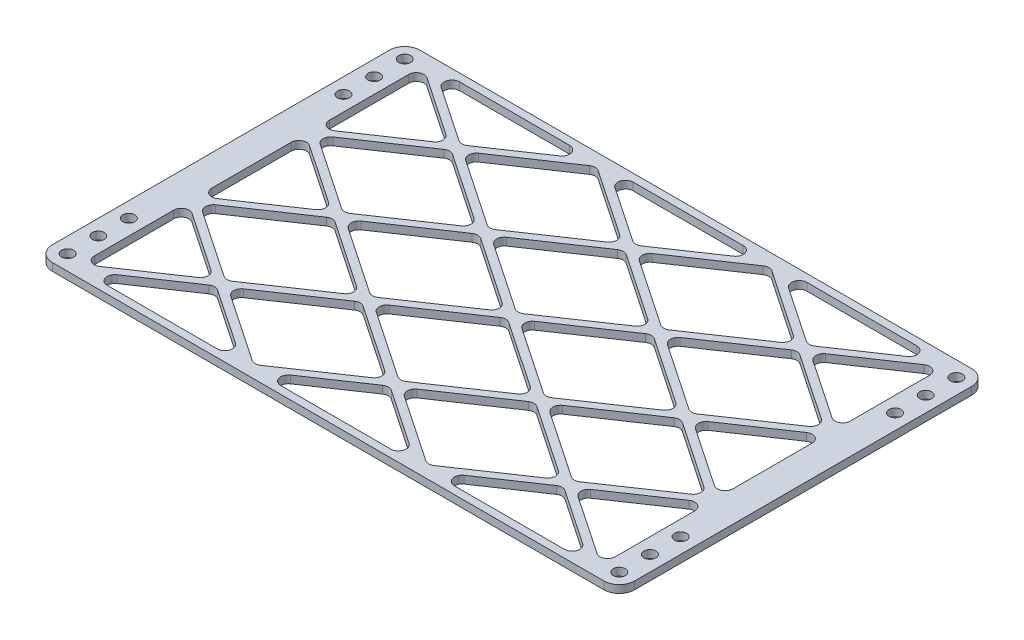
SolidWorks part; units mm, degrees
ref_plane "Front Plane" through (0, 0, 0) normal (0, 0, 1) x (1, 0, 0)
ref_plane "Top Plane" through (0, 0, 0) normal (0, 1, 0) x (1, 0, 0)
ref_plane "Right Plane" through (0, 0, 0) normal (1, 0, 0) x (0, 0, -1)
sketch "Sketch1" plane through (0, 0, 0) normal (0, 1, 0) x (1, 0, 0)
  line L0 (12.7, 152.4) -> (12.7, 0)
  line L1 (0, 0) -> (241.3, 0)
  line L2 (0, 0) -> (0, 152.4)
  line L3 (0, 152.4) -> (241.3, 152.4)
  line L4 (241.3, 0) -> (241.3, 152.4)
  line L5 (120.65, 152.4) -> (120.65, 0) construction
  line L6 (228.6, 152.4) -> (228.6, 0)
  line L7 (228.6, 3.175) -> (12.7, 149.225) construction
  line L8 (12.7, 149.225) -> (228.6, 149.225)
  line L9 (12.7, 3.175) -> (228.6, 3.175)
  line L10 (12.7, 100.5417) -> (84.6667, 100.5417)
  line L11 (84.6667, 100.5417) -> (84.6667, 149.225)
  line L12 (17.88, 147.6375) -> (15.5333, 149.225)
  line L13 (233.78, 1.5875) -> (17.88, 147.6375)
  line L14 (12.7, 100.5417) -> (84.6667, 149.225) construction
  line L15 (13.5895, 99.2268) -> (85.5562, 147.9101)
  line L16 (223.42, 4.7625) -> (7.52, 150.8125)
  line L17 (11.8105, 101.8566) -> (83.7772, 150.5399)
  line L18 (17.88, 147.6375) -> (228.6, 147.6375) construction
  line L19 (7.52, 150.8125) -> (228.6, 150.8125) construction
  line L20 (12.7, 4.7625) -> (223.42, 4.7625) construction
  line L21 (12.7, 1.5875) -> (233.78, 1.5875) construction
  circle A0 centre (6.35, 146.05) radius 2.4892
  circle A1 centre (6.35, 6.35) radius 2.4892
  dimension "D1" = 4.9784
  dimension "D2" = 139.7
  dimension "D3" = 6.35
  dimension "D4" = 6.35
  dimension "D5" = 6.35
  dimension "D6" = 241.3
  dimension "D7" = 6.35
  dimension "D8" = 3.175
  dimension "D9" = 3.175
  dimension "D10" = 71.9667
  dimension "D13" = 1.5875
  dimension "D11" = 1.5875
  dimension "D12" = 1.5875
  dimension "D14" = 1.5875
extrude "Boss-Extrude5" add sketch "Sketch1" along normal blind 3.175 contours L6 L13 L11 L10 L0 L9 | L3 L2 L1 L0 A1 A0 | L3 L6 L1 L4 | L9 L0 L1 L6 | L13 L6 L8 L11 | L13 L17 L8 L12 | L0 L8 L6 L3 | L15 L13 L11 | L17 L13 L15 L11 L8 | L17 L0 L10 L15 L16 | L17 L16 L15 L13 | L16 L17 L13 L12 L8 L0 | L16 L10 L11 L13 L15 | L0 L17 L16 | L10 L16 L15 region at (120.65, 0, -150.8125) region at (6.35, 0, -76.2) region at (30.335, 0, -137.2954) region at (234.95, 0, -76.2) region at (23.75, 0, -124.8833) region at (48.6833, 0, -141.75) region at (168.8686, 0, -97.3616) region at (30.335, 0, -112.4713) region at (48.6833, 0, -124.8833) region at (67.0316, 0, -137.2954) region at (120.65, 0, -1.5875) region at (91.9374, 0, -43.9196) region at (48.6833, 0, -108.0167) region at (67.0316, 0, -112.4713) region at (73.6166, 0, -124.8833)
extrude "Cut-Extrude7" cut sketch "Sketch1<6>" along normal blind 32.131 contours L10 L16 L15 | L0 L17 L16 | L13 L17 L8 L12 | L15 L13 L11 region at (23.75, 0, -124.8833) region at (48.6833, 0, -141.75) region at (48.6833, 0, -108.0167) region at (73.6166, 0, -124.8833)
sketch "Sketch1<6>" plane through (0, 0, 0) normal (0, 1, 0) x (1, 0, 0) same geometry as "Sketch1"
pattern_linear "LPattern3" count 3 spacing 71.9667 along (1, 0, 0) count 3 spacing 48.6833 along (0, 0, 1) of "Cut-Extrude7"
fillet "Fillet2" radius 3.175 84 edges at (156.6333, 1.5875, -49.9417) (123.4833, 1.5875, -27.5167) (156.6333, 1.5875, -5.0916) (189.7834, 1.5875, -27.5167) (84.6667, 1.5875, -49.9417) (51.5166, 1.5875, -27.5167) (84.6667, 1.5875, -5.0916) (117.8167, 1.5875, -27.5167) (45.8501, 1.5875, -27.5167) (12.7, 1.5875, -49.9417) (12.7, 1.5875, -5.0916) (156.6333, 1.5875, -147.3084) (123.4833, 1.5875, -124.8833) (156.6333, 1.5875, -102.4583) (189.7834, 1.5875, -124.8833) (45.8501, 1.5875, -76.2) (12.7, 1.5875, -98.6251) (12.7, 1.5875, -53.7749) (84.6667, 1.5875, -98.6251) (51.5166, 1.5875, -76.2) (84.6667, 1.5875, -53.7749) (117.8167, 1.5875, -76.2) (156.6333, 1.5875, -98.6251) (123.4833, 1.5875, -76.2) (156.6333, 1.5875, -53.7749) (189.7834, 1.5875, -76.2) (84.6667, 1.5875, -147.3084) (51.5166, 1.5875, -124.8833) (84.6667, 1.5875, -102.4583) (117.8167, 1.5875, -124.8833) (192.6167, 1.5875, -25.6001) (159.4666, 1.5875, -3.175) (225.7667, 1.5875, -3.175) (120.65, 1.5875, -25.6001) (87.4999, 1.5875, -3.175) (153.8001, 1.5875, -3.175) (48.6833, 1.5875, -25.6001) (15.5333, 1.5875, -3.175) (81.8334, 1.5875, -3.175) (159.4666, 1.5875, -100.5417) (192.6167, 1.5875, -78.1166) (225.7667, 1.5875, -100.5417) (192.6167, 1.5875, -122.9667) (15.5333, 1.5875, -51.8583) (48.6833, 1.5875, -29.4333) (81.8334, 1.5875, -51.8583) (48.6833, 1.5875, -74.2834) (87.4999, 1.5875, -51.8583) (120.65, 1.5875, -29.4333) (153.8001, 1.5875, -51.8583) (120.65, 1.5875, -74.2834) (159.4666, 1.5875, -51.8583) (192.6167, 1.5875, -29.4333) (225.7667, 1.5875, -51.8583) (192.6167, 1.5875, -74.2834) (87.4999, 1.5875, -100.5417) (120.65, 1.5875, -78.1166) (153.8001, 1.5875, -100.5417) (120.65, 1.5875, -122.9667) (45.8501, 1.5875, -124.8833) (12.7, 1.5875, -147.3084) (12.7, 1.5875, -102.4583) (48.6833, 1.5875, -126.7999) (15.5333, 1.5875, -149.225) (120.65, 1.5875, -126.7999) (153.8001, 1.5875, -149.225) (87.4999, 1.5875, -149.225) (48.6833, 1.5875, -78.1166) (81.8334, 1.5875, -100.5417) (48.6833, 1.5875, -122.9667) (15.5333, 1.5875, -100.5417) (192.6167, 1.5875, -126.7999) (225.7667, 1.5875, -149.225) (159.4666, 1.5875, -149.225) (195.4499, 1.5875, -76.2) (228.6, 1.5875, -53.7749) (228.6, 1.5875, -98.6251) (195.4499, 1.5875, -124.8833) (228.6, 1.5875, -102.4583) (228.6, 1.5875, -147.3084) (195.4499, 1.5875, -27.5167) (228.6, 1.5875, -5.0916) (228.6, 1.5875, -49.9417) (81.8334, 1.5875, -149.225)
fillet "Fillet3" radius 6.35 4 edges at (241.3, 1.5875, 0) (0, 1.5875, 0) (241.3, 1.5875, -152.4) (0, 1.5875, -152.4)
sketch "Sketch2" plane through (0, 3.175, 0) normal (0, 1, 0) x (1, 0, 0)
  line L0 (241.3, 6.35) -> (241.3, 146.05) construction
  line L1 (6.35, 152.4) -> (234.95, 152.4) construction
  line L2 (234.95, 146.05) -> (234.95, 133.35) construction
  line L3 (0, 6.35) -> (0, 146.05) construction
  line L4 (6.35, 133.35) -> (6.35, 120.65) construction
  circle A0 centre (234.95, 146.05) radius 2.4892
  circle A1 centre (234.95, 133.35) radius 2.4892
  circle A2 centre (234.95, 120.65) radius 2.4892
  circle A3 centre (234.95, 107.95) radius 2.4892
  circle A4 centre (234.95, 95.25) radius 2.4892
  circle A5 centre (234.95, 82.55) radius 2.4892
  circle A6 centre (234.95, 69.85) radius 2.4892
  circle A7 centre (234.95, 57.15) radius 2.4892
  circle A8 centre (234.95, 44.45) radius 2.4892
  circle A9 centre (234.95, 31.75) radius 2.4892
  circle A10 centre (234.95, 19.05) radius 2.4892
  circle A11 centre (234.95, 6.35) radius 2.4892
  circle A12 centre (6.35, 133.35) radius 2.4892
  circle A13 centre (6.35, 120.65) radius 2.4892
  circle A14 centre (6.35, 107.95) radius 2.4892
  circle A15 centre (6.35, 95.25) radius 2.4892
  circle A16 centre (6.35, 82.55) radius 2.4892
  circle A17 centre (6.35, 69.85) radius 2.4892
  circle A18 centre (6.35, 57.15) radius 2.4892
  circle A19 centre (6.35, 44.45) radius 2.4892
  circle A20 centre (6.35, 31.75) radius 2.4892
  circle A21 centre (6.35, 19.05) radius 2.4892
  dimension "D1" = 4.9784
  dimension "D6" = 6.35
  dimension "D2" = 6.35
  dimension "D3" = 6.35
  dimension "D5" = 12.7
  dimension "D8" = 12.7
  dimension "D4" = 12
  dimension "D7" = 10
extrude "Cut-Extrude8" cut sketch "Sketch2" against normal through all contours A12 | A13 | A21 | A20 | A11 | A10 | A9 | A1 | A0 | A2 region at (234.95, 3.175, -146.05) region at (234.95, 3.175, -133.35) region at (234.95, 3.175, -120.65) region at (234.95, 3.175, -31.75) region at (234.95, 3.175, -19.05) region at (234.95, 3.175, -6.35) region at (6.35, 3.175, -133.35) region at (6.35, 3.175, -120.65) region at (6.35, 3.175, -31.75) region at (6.35, 3.175, -19.05)
